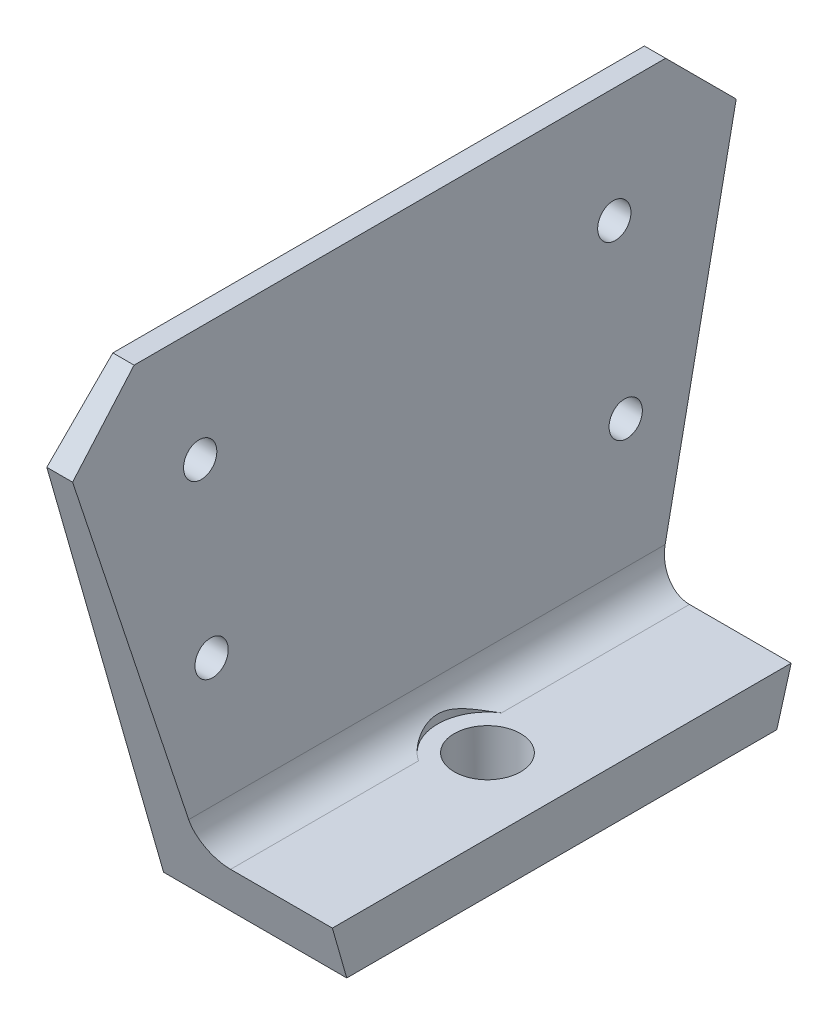
SolidWorks part; units mm, degrees
ref_plane "Front Plane" through (0, 0, 0) normal (0, 0, 1) x (1, 0, 0)
ref_plane "Top Plane" through (0, 0, 0) normal (0, 1, 0) x (1, 0, 0)
ref_plane "Right Plane" through (0, 0, 0) normal (1, 0, 0) x (0, 0, -1)
sketch "Sketch2" plane through (0, 0, 0) normal (1, 0, 0) x (0, 0, -1)
  line L0 (41.148, 0) -> (-41.148, 0)
  line L1 (-41.148, 0) -> (-63.5, 78.2912)
  line L2 (0, 0) -> (0, 90.932) construction
  line L3 (43.9036, 9.652) -> (-43.9036, 9.652)
  line L4 (-50.8592, 90.932) -> (50.8592, 90.932)
  line L5 (-63.5, 78.2912) -> (-50.8592, 90.932)
  line L6 (63.5, 78.2912) -> (50.8592, 90.932)
  line L7 (41.148, 0) -> (63.5, 78.2912)
  circle A0 centre (-39.624, 70.358) radius 3.175
  circle A1 centre (39.624, 38.608) radius 3.175
  circle A2 centre (-39.624, 38.608) radius 3.175
  circle A3 centre (39.624, 70.358) radius 3.175
  point P12 (0, 9.652)
  dimension "D7" = 6.35
  dimension "D1" = 41.148
  dimension "D2" = 90.932
  dimension "D3" = 12.6408
  dimension "D4" = 9.652
  dimension "D5" = 45
  dimension "D6" = 63.5
  dimension "D8" = 31.75
  dimension "D9" = 23.876
  dimension "D10" = 20.574
extrude "Boss-Extrude1" add sketch "Sketch2" along normal blind 9.652 contours L2 L3 L7 L6 L4 A1 A3 | L3 L2 L4 L5 L1 A2 A0 | L0 L2 L3 L1 | L2 L0 L7 L3 region at (0, 4.8781, -21.2703) region at (0, 4.8781, 21.2703) region at (0, 52.3099, -27.2261) region at (0, 52.3099, 27.2261)
extrude "Boss-Extrude2" add sketch "Sketch2<6>" along normal blind 35.052 contours L0 L2 L3 L1 | L2 L0 L7 L3 region at (0, 4.8781, -21.2703) region at (0, 4.8781, 21.2703)
sketch "Sketch2<6>" plane through (0, 0, 0) normal (1, 0, 0) x (0, 0, -1) same geometry as "Sketch2"
sketch "Sketch4" plane through (0, 0, 0) normal (0, 0, 1) x (1, 0, 0)
  line L0 (9.652, 9.652) -> (4.064, 90.932)
  line L1 (9.652, 90.932) -> (0, 90.932) construction
  line L2 (9.652, 9.652) -> (35.052, 9.652)
  line L3 (4.064, 90.932) -> (9.652, 90.932)
  line L4 (9.652, 90.932) -> (9.652, 9.652)
  dimension "D1" = 4.064
extrude "Cut-Extrude1" cut sketch "Sketch4" against normal through all and the other way through all contours L0 L3 L4
fillet "Fillet1" radius 6.35 1 edges at (9.652, 9.652, 0)
sketch "Sketch5" plane through (0, 9.652, 0) normal (0, 1, 0) x (1, 0, 0)
  line L0 (35.052, 43.9036) -> (35.052, -43.9036) construction
  line L1 (35.052, -43.9036) -> (15.5804, -43.9036) construction
  circle A0 centre (20.828, 0) radius 6.35
  dimension "D1" = 12.7
  dimension "D2" = 14.224
  dimension "D3" = 43.9036
extrude "Cut-Extrude3" cut sketch "Sketch5" against normal through all and the other way through all
sketch "Sketch6" plane through (0, 9.652, 0) normal (0, 1, 0) x (1, 0, 0)
  circle A0 centre (20.828, 0) radius 9.525
  dimension "D1" = 19.05
extrude "Cut-Extrude4" cut sketch "Sketch6" along normal through all
